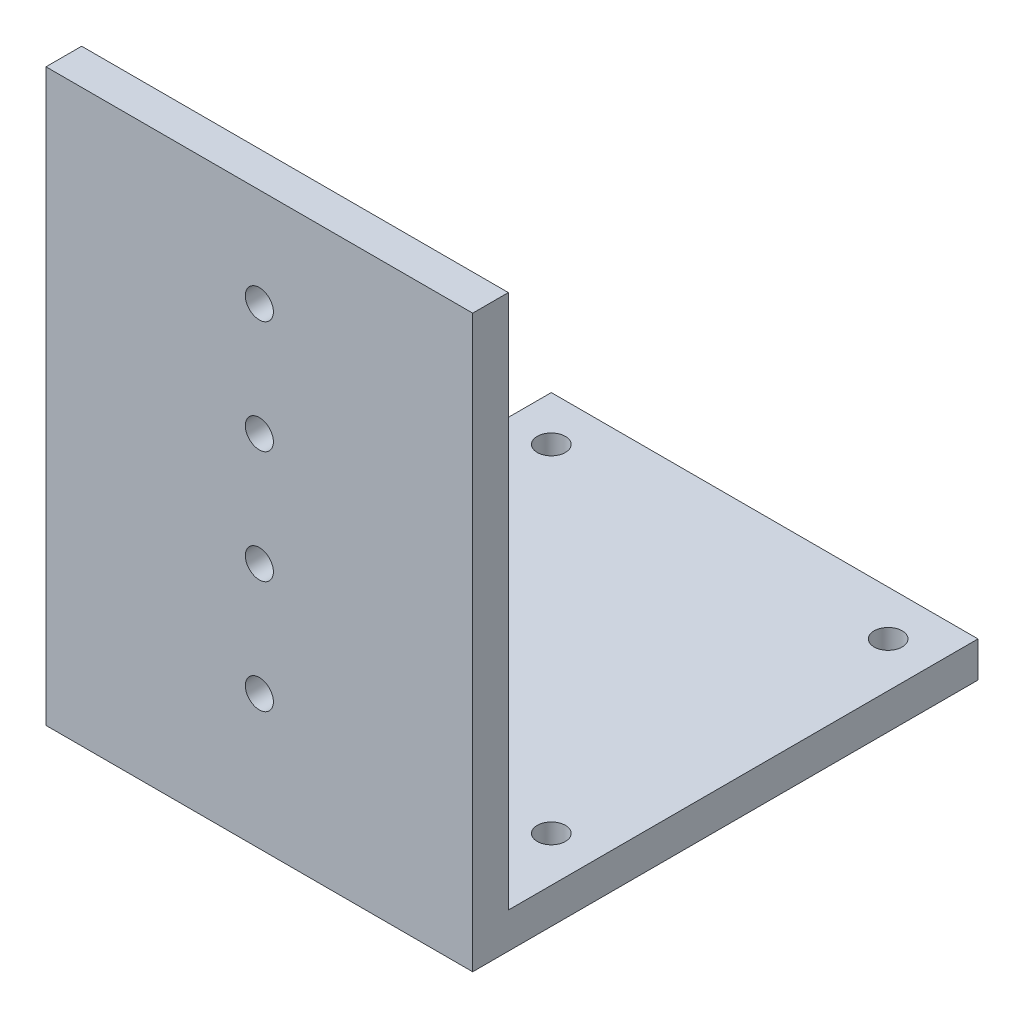
SolidWorks part; units mm, degrees
ref_plane "Front" through (0, 0, 0) normal (0, 0, 1) x (1, 0, 0)
ref_plane "Top" through (0, 0, 0) normal (0, 1, 0) x (1, 0, 0)
ref_plane "Right" through (0, 0, 0) normal (1, 0, 0) x (0, 0, -1)
sketch "Sketch1" plane through (0, 0, 0) normal (0, 1, 0) x (1, 0, 0)
  line L1 (0, 0) -> (38, 0)
  line L2 (0, 0) -> (0, -45)
  line L3 (0, -45) -> (38, -45)
  line L4 (38, 0) -> (38, -45)
  dimension "D1" = 38
  dimension "D2" = 45
extrude "Boss-Extrude1" add sketch "Sketch1" along normal blind 3.175
sketch "Sketch2" plane through (0, 3.175, 0) normal (0, 1, 0) x (1, 0, 0)
  line L0 (38, -45) -> (38, 0) construction
  line L1 (0, -45) -> (38, -45)
  line L2 (0, -45) -> (0, -41.825)
  line L3 (0, -41.825) -> (38, -41.825)
  line L4 (38, -45) -> (38, -41.825)
  dimension "D1" = 3.175
extrude "Boss-Extrude2" add sketch "Sketch2" along normal blind 47.625
sketch "Sketch3" plane through (0, 0, 0) normal (0, -1, 0) x (1, 0, 0)
  line L0 (0, 0) -> (0, 45) construction
  line L1 (38, 45) -> (38, 0) construction
  line L3 (38, 0) -> (0, 0) construction
  circle A0 centre (4, 34) radius 1.25
  circle A1 centre (34, 34) radius 1.25
  circle A2 centre (4, 4) radius 1.25
  circle A4 centre (34, 4) radius 1.25
  dimension "D1" = 2.5
  dimension "D2" = 2.5
  dimension "D3" = 2.5
  dimension "D4" = 2.5
  dimension "D5" = 4
  dimension "D6" = 4
  dimension "D7" = 4
  dimension "D8" = 4
  dimension "D9" = 4
  dimension "D10" = 4
  dimension "D11" = 34
  dimension "D12" = 34
extrude "camera holes" cut sketch "Sketch3" against normal blind 10
sketch "Sketch4" plane through (0, 0, 45) normal (0, 0, 1) x (1, 0, 0)
  line L0 (0, 50.8) -> (0, 0) construction
  line L1 (0, 50.8) -> (38, 50.8) construction
  circle A0 centre (19, 42.025) radius 1.25
  circle A1 centre (19, 11.95) radius 1.25
  circle A2 centre (19, 32) radius 1.25
  circle A3 centre (19, 21.975) radius 1.25
  point P2 (18.0147, 48.3054)
  point P7 (19, 5.6177)
  point P10 (19, 35.1163)
  point P13 (19, 20.367)
  point P14 (19, 8.2304)
  dimension "D1" = 2.5
  dimension "D2" = 19
  dimension "D3" = 8.775
  dimension "D4" = 10.025
  dimension "D5" = 10.025
  dimension "D6" = 10.025
extrude "mounting holes" cut sketch "Sketch4" against normal blind 10
